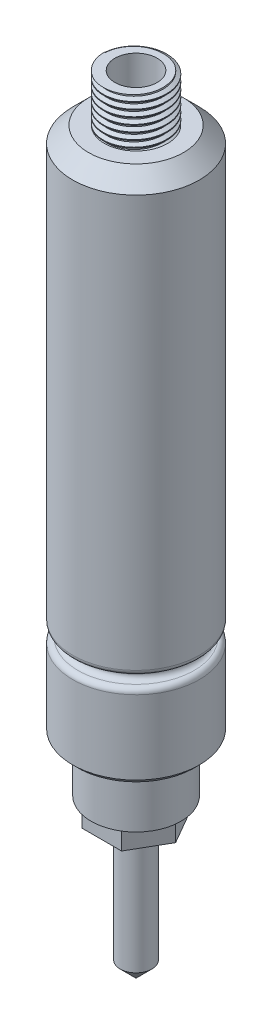
SolidWorks part; units mm, degrees
ref_plane "Front Plane" through (0, 0, 0) normal (0, 0, 1) x (1, 0, 0)
ref_plane "Top Plane" through (0, 0, 0) normal (0, 1, 0) x (1, 0, 0)
ref_plane "Right Plane" through (0, 0, 0) normal (1, 0, 0) x (0, 0, -1)
sketch "Sketch1" plane through (0, 0, 0) normal (0, 1, 0) x (1, 0, 0)
  circle A0 centre (0, 0) radius 12
  dimension "D1" = 24
extrude "Boss-Extrude1" add sketch "Sketch1" along normal blind 90
sketch "Sketch2" plane through (0, 0, 0) normal (0, -1, 0) x (1, 0, 0)
  circle A0 centre (0, 0) radius 8.5
  circle A1 centre (0, 0) radius 12
  dimension "D1" = 17
extrude "Cut-Extrude1" cut sketch "Sketch2" against normal blind 10
sketch "Sketch3" plane through (0, 0, 0) normal (1, 0, 0) x (0, 0, -1)
  line L0 (-12, 10) -> (-12, 26)
  line L1 (-12, 90) -> (-12, 10) construction
  line L2 (0, 90) -> (0, 0) construction
  line L3 (-12, 26) -> (-10, 26)
  line L4 (-12, 26) -> (-12, 28)
  line L5 (-12, 28) -> (-10, 28)
  line L6 (-10, 26) -> (-10, 28)
  line L7 (12, 90) -> (-12, 90) construction
  dimension "D1" = 16
  dimension "D2" = 2
  dimension "D3" = 2
revolve "Cut-Revolve1" cut sketch "Sketch3" angle 360 about L2 region at (0, 27, 11)
sketch "Sketch4" plane through (0, 90, 0) normal (0, 1, 0) x (1, 0, 0)
  circle A0 centre (0, 0) radius 12
extrude "Boss-Extrude2" add sketch "Sketch4" along normal blind 20
sketch "Sketch5" plane through (0, 0, 0) normal (0, -1, 0) x (1, 0, 0)
  circle A0 centre (0, 0) radius 3
  dimension "D1" = 6
extrude "Boss-Extrude3" add sketch "Sketch5" along normal blind 30
chamfer "Chamfer1" distance 3 angle 45 1 edges at (0, -30, -3)
sketch "Sketch6" plane through (0, 110, 0) normal (0, 1, 0) x (1, 0, 0)
  circle A0 centre (0, 0) radius 6
  dimension "D1" = 12
extrude "Boss-Extrude4" add sketch "Sketch6" along normal blind 10
thread "Thread1" pitch 1.25 method cut profile "Thread Profile2" start angle 0, offset 0, length 0, pitch 1.25, diameter 12
ref_plane "Plane2" through (-6, 120, 0) normal (0, 0, 1) x (-1, 0, 0)
sketch "Thread Profile2" plane through (-6, 120, 0) normal (0, 0, 1) x (-1, 0, 0)
  line L0 (0, 0) -> (0, 1.25) construction
  line L11 (0, 0) -> (0, 1.0937)
  line L12 (0, 1.0937) -> (-0.6766, 0.7031)
  line L13 (-0.6766, 0.7031) -> (-0.6766, 0.3906)
  line L15 (-0.6766, 0.3906) -> (0, 0)
  line L17 (-0.6766, 0.5469) -> (0, 0.5469) construction
  point P2 (0, 0)
  dimension "Pitch" = 1.25
  dimension "Profile_Angle" = 60
  dimension "Profile_Land" = 0.3125
  dimension "Profile_Height" = 0.6766
sketch "Sketch15" plane through (0, 120, 0) normal (0, 1, 0) x (1, 0, 0)
  circle A0 centre (0, 0) radius 6
extrude "Cut-Extrude2" cut sketch "Sketch15" against normal blind 1
chamfer "Chamfer2" distance 1 angle 45 1 edges at (0, 10, -12)
sketch "Sketch16" plane through (0, 0, 0) normal (0, -1, 0) x (1, 0, 0)
  line L1 (7.5, 0) -> (3.75, 6.4952)
  line L2 (3.75, 6.4952) -> (-3.75, 6.4952)
  line L3 (-3.75, 6.4952) -> (-7.5, 0)
  line L4 (-7.5, 0) -> (-3.75, -6.4952)
  line L5 (-3.75, -6.4952) -> (3.75, -6.4952)
  line L6 (3.75, -6.4952) -> (7.5, 0)
  circle A0 centre (0, 0) radius 7.5
  circle A1 centre (0, 0) radius 6.4952 construction
  circle M1 centre (0, 0) radius 3
  dimension "D1" = 15
extrude "Boss-Extrude5" add sketch "Sketch16" along normal blind 4 contours L5 L6 L1 L2 L3 L4 M1 region at (5.4532, 0, -3.1484)
fillet "Fillet1" radius 1 2 edges at (0, 26, 10) (0, 28, 10)
fillet "Fillet2" radius 1 2 edges at (0, 26, 12) (0, 28, 12)
sketch "Sketch17" plane through (0, 119, 0) normal (0, 1, 0) x (1, 0, 0)
  circle A0 centre (0, 0) radius 4
  dimension "D1" = 8
extrude "Cut-Extrude3" cut sketch "Sketch17" against normal up to surface (119 mm away) up to face at (0, 0, -8.5)
fillet "Fillet3" radius 3 1 edges at (0, 0, 4)
sketch "Sketch18" plane through (0, -4, 0) normal (0, -1, 0) x (1, 0, 0)
  circle A0 centre (0, 0) radius 0.13
  dimension "D1" = 0.26
extrude "Cut-Extrude4" cut sketch "Sketch18" along normal blind 50
sketch "Sketch20" plane through (0, -4, 0) normal (0, -1, 0) x (1, 0, 0)
  circle A0 centre (0, 0) radius 0.13
extrude "Cut-Extrude5" cut sketch "Sketch20" against normal blind 18
sketch "Sketch21" plane through (0, 110, 0) normal (0, 1, 0) x (1, 0, 0)
  line L0 (-12, 0) -> (-10, 0)
  line L1 (-10, 6.6332) -> (-10, -6.6332)
  circle A0 centre (0, 0) radius 12
  circle M5 centre (0, 0) radius 12
  dimension "D1" = 2
extrude "Cut-Extrude6" cut sketch "Sketch21" against normal blind 60 contours L1 L0 M5 | L1 L0 M5 region at (-10.806, 110, -2.5176) region at (-10.806, 110, 2.5176)
extrude "Boss-Extrude6" add sketch "Sketch21<3>" against normal blind 20 contours L1 L0 M5 | L1 L0 M5 region at (-10.806, 110, -2.5176) region at (-10.806, 110, 2.5176)
sketch "Sketch21<3>" plane through (0, 110, 0) normal (0, 1, 0) x (1, 0, 0) same geometry as "Sketch21"
chamfer "Chamfer3" distance 3 angle 45 1 edges at (0, 110, 12)
